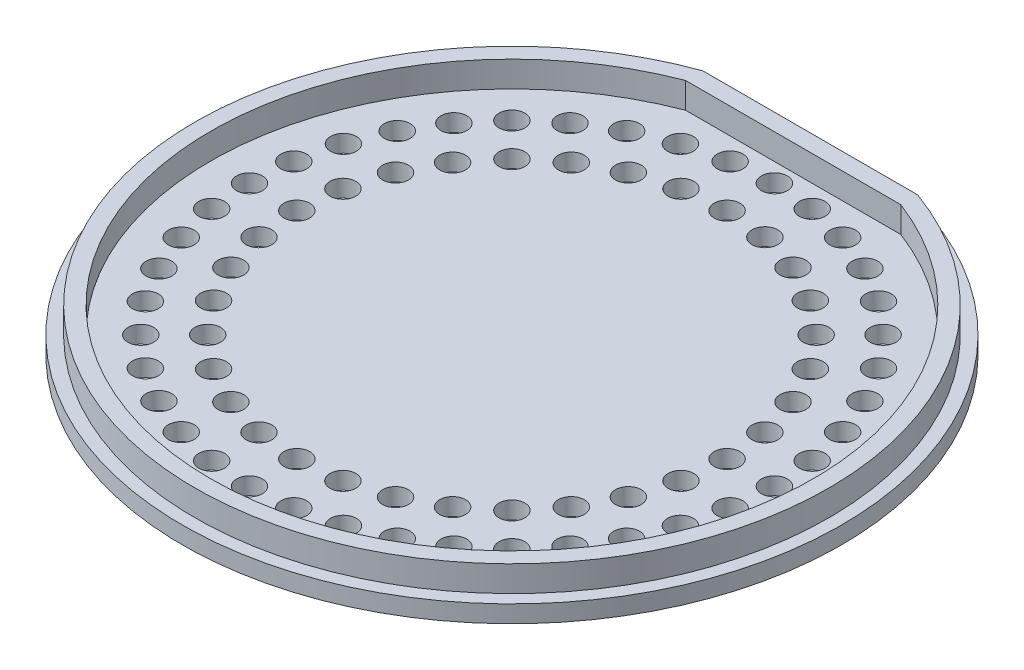
SolidWorks part; units mm, degrees
note: The reader was unsure of these and kept them because the rebuilt part matched: shared geometry of "Sketch1<4>".
ref_plane "Front Plane" through (0, 0, 0) normal (0, 0, 1) x (1, 0, 0)
ref_plane "Top Plane" through (0, 0, 0) normal (0, 1, 0) x (1, 0, 0)
ref_plane "Right Plane" through (0, 0, 0) normal (1, 0, 0) x (0, 0, -1)
sketch "Sketch1" plane through (0, 0, 0) normal (0, 1, 0) x (1, 0, 0)
  line L0 (0, -36.8392) -> (0, 34.6608) construction
  line L1 (-12.4804, 34.6608) -> (12.4804, 34.6608)
  line L2 (0, 34.6608) -> (0, 10.8) construction
  line L3 (-12.5, 32.6917) -> (12.5, 32.6917)
  line L5 (0, -36.8392) -> (0, -26.1825) construction
  line L6 (12.4804, 36.421) -> (-12.4804, 36.421)
  line L7 (0, 0) -> (0, 11.9) construction
  line L8 (0, 0) -> (0, -26.1295) construction
  arc A0 (-12.4804, 34.6608) -> (12.4804, 34.6608) centre (0, 0) ccw
  arc A3 (-12.4804, 36.421) -> (12.4804, 36.421) centre (0, 0) ccw
  arc A4 (-12.5, 32.6917) -> (12.5, 32.6917) centre (0, 0) ccw
  circle A5 centre (0, 0) radius 30.5
  circle A8 centre (0, 30.5) radius 1.5
  circle A9 centre (4.7713, 30.1245) radius 1.5
  circle A10 centre (9.425, 29.0072) radius 1.5
  circle A11 centre (13.8467, 27.1757) radius 1.5
  circle A12 centre (17.9275, 24.675) radius 1.5
  circle A13 centre (21.5668, 21.5668) radius 1.5
  circle A14 centre (24.675, 17.9275) radius 1.5
  circle A15 centre (27.1757, 13.8467) radius 1.5
  circle A16 centre (29.0072, 9.425) radius 1.5
  circle A17 centre (30.1245, 4.7713) radius 1.5
  circle A18 centre (30.5, 0) radius 1.5
  circle A19 centre (30.1245, -4.7713) radius 1.5
  circle A20 centre (29.0072, -9.425) radius 1.5
  circle A21 centre (27.1757, -13.8467) radius 1.5
  circle A22 centre (24.675, -17.9275) radius 1.5
  circle A23 centre (21.5668, -21.5668) radius 1.5
  circle A24 centre (17.9275, -24.675) radius 1.5
  circle A25 centre (13.8467, -27.1757) radius 1.5
  circle A26 centre (9.425, -29.0072) radius 1.5
  circle A27 centre (4.7713, -30.1245) radius 1.5
  circle A28 centre (0, -30.5) radius 1.5
  circle A29 centre (-4.7713, -30.1245) radius 1.5
  circle A30 centre (-9.425, -29.0072) radius 1.5
  circle A31 centre (-13.8467, -27.1757) radius 1.5
  circle A32 centre (-17.9275, -24.675) radius 1.5
  circle A33 centre (-21.5668, -21.5668) radius 1.5
  circle A34 centre (-24.675, -17.9275) radius 1.5
  circle A35 centre (-27.1757, -13.8467) radius 1.5
  circle A36 centre (-29.0072, -9.425) radius 1.5
  circle A37 centre (-30.1245, -4.7713) radius 1.5
  circle A38 centre (-30.5, 0) radius 1.5
  circle A39 centre (-30.1245, 4.7713) radius 1.5
  circle A40 centre (-29.0072, 9.425) radius 1.5
  circle A41 centre (-27.1757, 13.8467) radius 1.5
  circle A42 centre (-24.675, 17.9275) radius 1.5
  circle A43 centre (-21.5668, 21.5668) radius 1.5
  circle A44 centre (-17.9275, 24.675) radius 1.5
  circle A45 centre (-13.8467, 27.1757) radius 1.5
  circle A46 centre (-9.425, 29.0072) radius 1.5
  circle A47 centre (-4.7713, 30.1245) radius 1.5
  circle A48 centre (0, 0) radius 25
  circle A49 centre (0, 25) radius 1.5
  circle A50 centre (4.8773, 24.5196) radius 1.5
  circle A51 centre (9.5671, 23.097) radius 1.5
  circle A52 centre (13.8893, 20.7867) radius 1.5
  circle A53 centre (17.6777, 17.6777) radius 1.5
  circle A54 centre (20.7867, 13.8893) radius 1.5
  circle A55 centre (23.097, 9.5671) radius 1.5
  circle A56 centre (24.5196, 4.8773) radius 1.5
  circle A57 centre (25, 0) radius 1.5
  circle A58 centre (24.5196, -4.8773) radius 1.5
  circle A59 centre (23.097, -9.5671) radius 1.5
  circle A60 centre (20.7867, -13.8893) radius 1.5
  circle A61 centre (17.6777, -17.6777) radius 1.5
  circle A62 centre (13.8893, -20.7867) radius 1.5
  circle A63 centre (9.5671, -23.097) radius 1.5
  circle A64 centre (4.8773, -24.5196) radius 1.5
  circle A65 centre (0, -25) radius 1.5
  circle A66 centre (-4.8773, -24.5196) radius 1.5
  circle A67 centre (-9.5671, -23.097) radius 1.5
  circle A68 centre (-13.8893, -20.7867) radius 1.5
  circle A69 centre (-17.6777, -17.6777) radius 1.5
  circle A70 centre (-20.7867, -13.8893) radius 1.5
  circle A71 centre (-23.097, -9.5671) radius 1.5
  circle A72 centre (-24.5196, -4.8773) radius 1.5
  circle A73 centre (-25, 0) radius 1.5
  circle A74 centre (-24.5196, 4.8773) radius 1.5
  circle A75 centre (-23.097, 9.5671) radius 1.5
  circle A76 centre (-20.7867, 13.8893) radius 1.5
  circle A77 centre (-17.6777, 17.6777) radius 1.5
  circle A78 centre (-13.8893, 20.7867) radius 1.5
  circle A79 centre (-9.5671, 23.097) radius 1.5
  circle A80 centre (-4.8773, 24.5196) radius 1.5
  point P8 (0, 36.421)
  point P165 (0, 0)
  point P180 (0, 0)
  dimension "D3" = 36.8392
  dimension "D4" = 38.5
  dimension "D5" = 35
  dimension "D6" = 25
  dimension "D7" = 50
  dimension "D8" = 61
  dimension "D9" = 3
  dimension "D11" = 3
  dimension "D12" = 32
  dimension "D1" = 34.6608
  dimension "D2" = 36.421
  dimension "D10" = 40
extrude "Boss-Extrude1" add sketch "Sketch1" along normal blind 3 contours L1 A0 A4 L3
extrude "Boss-Extrude3" add sketch "Sketch1<4>" against normal blind 2
sketch "Sketch1<4>" plane through (0, 0, 0) normal (0, 1, 0) x (1, 0, 0) same geometry as "Sketch1"
sketch "Sketch2" plane through (0, 0, 0) normal (0, 1, 0) x (1, 0, 0)
  line L2 (12.447, 36.221) -> (-12.447, 36.221)
  line L3 (12.447, 36.221) -> (-12.447, 36.221)
  arc A4 (-12.447, 36.221) -> (12.447, 36.221) centre (0, 0) ccw
  arc A5 (-12.447, 36.221) -> (12.447, 36.221) centre (0, 0) ccw
  dimension "D1" = 0.2
extrude "Cut-Extrude2" cut sketch "Sketch2" against normal blind 10 flip side to cut
sketch "Sketch3" plane through (0, 0, 0) normal (0, 1, 0) x (1, 0, 0)
  line L2 (12.4454, 34.4608) -> (-12.4454, 34.4608)
  line L3 (12.4454, 34.4608) -> (-12.4454, 34.4608)
  arc A2 (-12.4454, 34.4608) -> (12.4454, 34.4608) centre (0, 0) ccw
  arc A3 (-12.4454, 34.4608) -> (12.4454, 34.4608) centre (0, 0) ccw
  dimension "D1" = 0.2
extrude "Cut-Extrude3" [suppressed] cut sketch "Sketch3" along normal blind 10 flip side to cut
